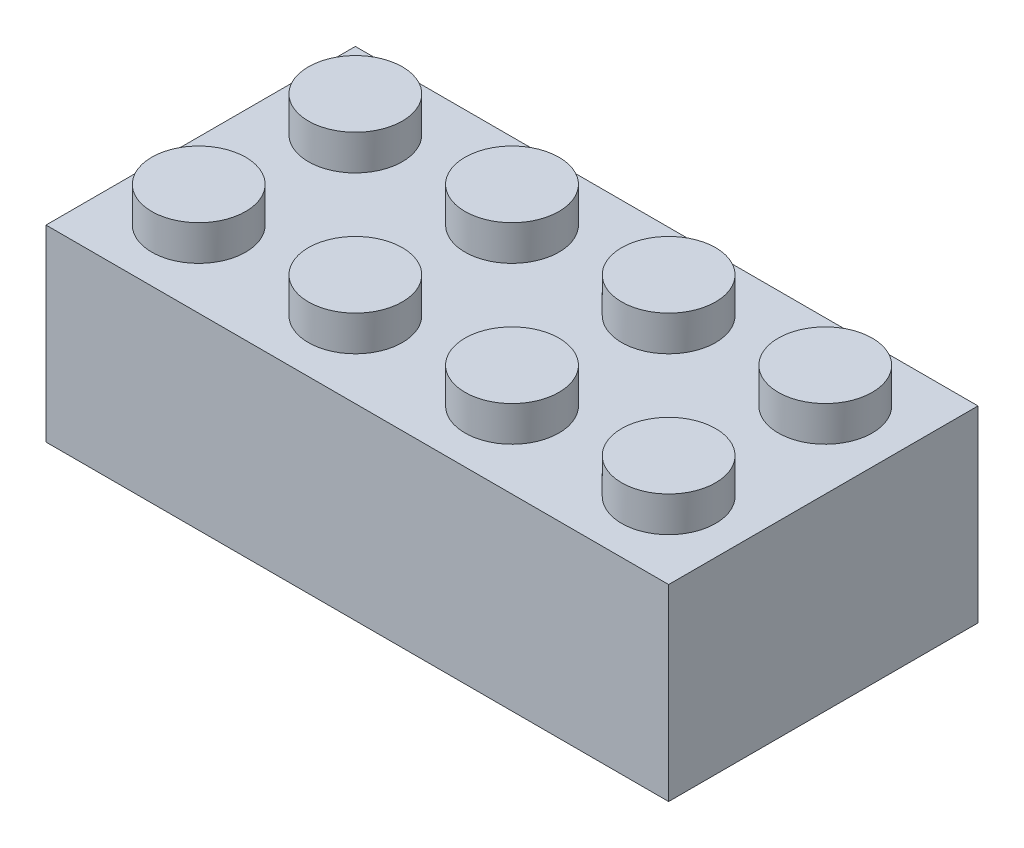
SolidWorks part; units mm, degrees
ref_plane "Front Plane" through (0, 0, 0) normal (0, 0, 1) x (1, 0, 0)
ref_plane "Top Plane" through (0, 0, 0) normal (0, 1, 0) x (1, 0, 0)
ref_plane "Right Plane" through (0, 0, 0) normal (1, 0, 0) x (0, 0, -1)
sketch "Sketch1" plane through (0, 0, 0) normal (0, 1, 0) x (1, 0, 0)
  line L1 (0, 0) -> (31.8, 0)
  line L2 (0, 0) -> (0, 15.8)
  line L3 (0, 15.8) -> (31.8, 15.8)
  line L4 (31.8, 0) -> (31.8, 15.8)
  dimension "D1" = 31.8
  dimension "D2" = 15.8
extrude "Boss-Extrude1" add sketch "Sketch1" along normal blind 9.6
shell "Shell1" thickness 1.2 removed face at (15.9, 0, -7.9)
sketch "Sketch2" plane through (0, 9.6, 0) normal (0, 1, 0) x (1, 0, 0)
  line L0 (31.8, 0) -> (31.8, 15.8) construction
  line L1 (31.8, 15.8) -> (0, 15.8) construction
  circle A0 centre (27.9, 11.9) radius 2.4
  circle A1 centre (19.9, 11.9) radius 2.4
  circle A2 centre (11.9, 11.9) radius 2.4
  circle A3 centre (3.9, 11.9) radius 2.4
  circle A4 centre (19.9, 3.9) radius 2.4
  circle A5 centre (11.9, 3.9) radius 2.4
  circle A6 centre (3.9, 3.9) radius 2.4
  circle A7 centre (27.9, 3.9) radius 2.4
  dimension "D1" = 4.8
  dimension "D2" = 3.9
  dimension "D3" = 3.9
  dimension "D4" = 4
  dimension "D5" = 2
extrude "Boss-Extrude2" add sketch "Sketch2" along normal blind 1.8
sketch "Sketch3" plane through (0, 8.4, 0) normal (0, -1, 0) x (-1, 0, 0)
  line L0 (0, 15.8) -> (0, 0) construction
  line L5 (0, 0) -> (-31.8, 0) construction
  circle A0 centre (-3.9, 3.9) radius 1.4
  circle A1 centre (-11.9, 3.9) radius 1.4
  circle A2 centre (-19.9, 3.9) radius 1.4
  circle A3 centre (-27.9, 3.9) radius 1.4
  circle A4 centre (-11.9, 11.9) radius 1.4
  circle A5 centre (-19.9, 11.9) radius 1.4
  circle A6 centre (-27.9, 11.9) radius 1.4
  circle A7 centre (-3.9, 11.9) radius 1.4
  dimension "D1" = 2.8
  dimension "D2" = 3.9
  dimension "D3" = 3.9
  dimension "D4" = 4
  dimension "D5" = 2
extrude "Cut-Extrude1" cut sketch "Sketch3" against normal blind 1.7
sketch "Sketch5" plane through (0, 8.4, 0) normal (0, -1, 0) x (1, 0, 0)
  line L0 (1.2, -8.1839) -> (30.6, -8.1839) construction
  line L1 (1.2, -14.6) -> (1.2, -1.2) construction
  line L2 (30.6, -1.2) -> (30.6, -14.6) construction
  line L3 (30.6, -8.1839) -> (15.9, -8.1839)
  line L4 (15.9, -8.1839) -> (15.9, -14.6) construction
  line L5 (30.6, -14.6) -> (1.2, -14.6) construction
  line L6 (1.2, -1.2) -> (30.6, -1.2) construction
  line L7 (16.3, -14.6) -> (15.5, -14.6)
  line L8 (16.3, -14.6) -> (16.3, -1.2)
  line L9 (16.3, -1.2) -> (15.5, -1.2)
  line L10 (15.5, -14.6) -> (15.5, -1.2)
  line M13 (1.2, -14.6) -> (30.6, -14.6)
  line M15 (30.6, -1.2) -> (1.2, -1.2)
  dimension "D1" = 0.8
  dimension "D2" = 0.4
extrude "Boss-Extrude3" add sketch "Sketch5" along normal blind 6.3 contours L10 L8 M13 M15 region at (15.9, 8.4, -7.9)
sketch "Sketch7" plane through (0, 0, -15.8) normal (0, 0, -1) x (-1, 0, 0)
  line L0 (-31.8, 2.6129) -> (0, 2.6129) construction
  line L1 (-31.8, 9.6) -> (-31.8, 0) construction
  line L2 (0, 9.6) -> (0, 0) construction
  text T0 "RUSSELL"
extrude "Cut-Extrude2" cut sketch "Sketch7" against normal blind 1.21
sketch "Sketch9" plane through (0, 0, -15.8) normal (0, 0, -1) x (-1, 0, 0)
  line L5 (-24.4705, 6.1129) -> (-23.7701, 6.1129) construction
  line L6 (-24.1564, 4.2283) -> (-23.9013, 4.2283)
  line L7 (-24.1564, 4.2283) -> (-24.1564, 6.1129)
  line L8 (-24.1564, 6.1129) -> (-23.9013, 6.1129)
  line L9 (-23.9013, 4.2283) -> (-23.9013, 6.1129)
extrude "Boss-Extrude5" add sketch "Sketch9" against normal blind 1.2
